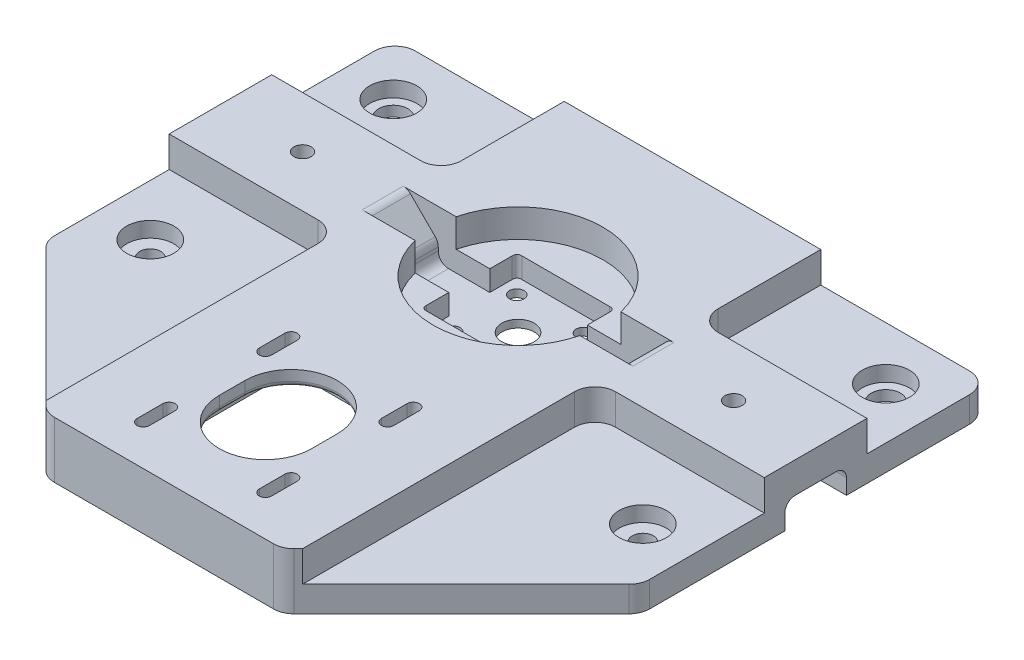
SolidWorks part; units mm, degrees
ref_plane "Front Plane" through (0, 0, 0) normal (0, 0, 1) x (1, 0, 0)
ref_plane "Top Plane" through (0, 0, 0) normal (0, 1, 0) x (1, 0, 0)
ref_plane "Right Plane" through (0, 0, 0) normal (1, 0, 0) x (0, 0, -1)
sketch "Sketch2" plane through (0, 0, 0) normal (0, 1, 0) x (1, 0, 0)
  line L2 (0, 33.02) -> (0, 0)
  line L3 (0, 0) -> (22.86, 0) construction
  line L4 (22.86, 0) -> (55.901, 38.5867) construction
  line L5 (55.901, 38.5867) -> (106.701, 38.5867) construction
  line L6 (106.701, 38.5867) -> (106.701, 56.3667)
  line L7 (0, 86.36) -> (0, 53.34)
  line L9 (0, 86.36) -> (20.32, 86.36)
  line L10 (20.32, 86.36) -> (106.701, 56.3667) construction
  line L11 (0, 53.34) -> (0, 33.02)
  line L12 (22.86, 0) -> (147.32, 0) construction
  line L13 (147.32, 0) -> (147.32, 86.36)
  line L14 (147.32, 86.36) -> (20.32, 86.36)
  line L15 (134.62, 73.2536) -> (134.62, 13.1064) construction
  line L16 (12.7, 73.2536) -> (134.62, 73.2536) construction
  line L17 (12.7, 73.2536) -> (12.7, 13.1064) construction
  line L18 (12.7, 13.1064) -> (134.62, 13.1064) construction
  line L19 (0, 0) -> (44.45, -44.45)
  line L20 (44.45, -44.45) -> (102.87, -44.45)
  line L21 (102.87, -44.45) -> (147.32, 0)
  line L22 (12.7, 73.2536) -> (0, 73.2536) construction
  line L23 (134.62, 73.2536) -> (147.32, 73.2536) construction
  line L24 (12.7, 13.1064) -> (12.7, 0) construction
  line L25 (12.7, 73.2536) -> (12.7, 86.36) construction
  circle A2 centre (12.7, 13.1064) radius 2.6035
  circle A3 centre (12.7, 73.2536) radius 3.6195
  circle A4 centre (73.681, 48.7467) radius 2.54 construction
  circle A5 centre (134.62, 73.2536) radius 3.6195
  circle A6 centre (134.62, 13.1064) radius 2.6035
  dimension "D11" = 121.92
  dimension "D20" = 7.239
  dimension "D22" = 5.08
  dimension "D9" = 5.207
  dimension "D1" = 50.8
  dimension "D2" = 50.8
  dimension "D3" = 22.86
  dimension "D4" = 33.02
  dimension "D5" = 20.32
  dimension "D6" = 20.32
  dimension "D7" = 91.44
  dimension "D8" = 17.78
  dimension "D12" = 60.1472
  dimension "D13" = 45
  dimension "D14" = 44.45
  dimension "D21" = 10.16
  dimension "D23" = 33.02
  dimension "D24" = 147.32
extrude "Boss-Extrude1" add sketch "Sketch2" along normal blind 6.35 contours L13 L14 L9 L7 L11 L2 L3 L12 A6 A5 A3 A2 region at (73.66, 0, -26.545)
sketch "Sketch3" plane through (0, 6.35, 0) normal (0, 1, 0) x (1, 0, 0)
  line L0 (12.7, 73.2536) -> (12.7, 13.1064) construction
  line L1 (134.62, 43.18) -> (12.7, 43.18) construction
  line L2 (134.62, 13.1064) -> (134.62, 73.2536) construction
  line L3 (0, 86.36) -> (0, 0) construction
  line L4 (147.32, 0) -> (147.32, 86.36) construction
  circle A0 centre (20.32, 43.18) radius 2.1273
  circle A1 centre (127, 43.18) radius 2.1273
  dimension "D1" = 4.2545
  dimension "D2" = 4.2545
  dimension "D3" = 20.32
  dimension "D4" = 20.32
extrude "Cut-Extrude1" cut sketch "Sketch3" against normal through all
sketch "Sketch4" plane through (0, 6.35, 0) normal (0, 1, 0) x (1, 0, 0)
  line L0 (20.32, 43.18) -> (127, 43.18) construction
  circle A0 centre (73.66, 43.18) radius 4.0005
  dimension "D1" = 8.001
extrude "Cut-Extrude2" cut sketch "Sketch4" against normal through all
sketch "Sketch5" plane through (0, 6.35, 0) normal (0, 1, 0) x (1, 0, 0)
  line L0 (147.32, 86.36) -> (0, 86.36) construction
  line L2 (41.91, 0) -> (41.91, 86.36) construction
  line L3 (41.91, 86.36) -> (105.41, 86.36)
  line L4 (105.41, 0) -> (105.41, 86.36) construction
  line L5 (41.91, 0) -> (105.41, 86.36) construction
  line L6 (41.91, 86.36) -> (105.41, 0) construction
  line L13 (44.45, -44.45) -> (102.87, -44.45) construction
  line L14 (44.45, -44.45) -> (102.87, -44.45)
  line L16 (105.41, 0) -> (105.41, -41.91)
  line L17 (102.87, -44.45) -> (147.32, 0) construction
  line L18 (105.41, -41.91) -> (102.87, -44.45)
  line L19 (41.91, 0) -> (41.91, -41.91)
  line L20 (0, 0) -> (44.45, -44.45) construction
  line L21 (41.91, -41.91) -> (44.45, -44.45)
  line L22 (0, 55.88) -> (0, 30.48)
  line L23 (0, 86.36) -> (0, 0) construction
  line L24 (0, 30.48) -> (41.91, 30.48)
  line L25 (41.91, 30.48) -> (41.91, 0)
  line L26 (0, 55.88) -> (41.91, 55.88)
  line L27 (41.91, 55.88) -> (41.91, 86.36)
  line L28 (105.41, 86.36) -> (105.41, 55.88)
  line L29 (105.41, 55.88) -> (147.32, 55.88)
  line L30 (147.32, 0) -> (147.32, 86.36) construction
  line L31 (147.32, 55.88) -> (147.32, 30.48)
  line L32 (147.32, 30.48) -> (105.41, 30.48)
  line L33 (105.41, 30.48) -> (105.41, 0)
  line L34 (127, 43.18) -> (147.32, 43.18) construction
  line L35 (0, 43.18) -> (20.32, 43.18) construction
  line L36 (20.32, 43.18) -> (127, 43.18) construction
  circle A0 centre (73.66, 43.18) radius 4.0005
  circle A1 centre (73.66, 43.18) radius 4.0005 construction
  point P0 (73.66, 43.18)
  dimension "D1" = 63.5
  dimension "D2" = 25.4
extrude "Boss-Extrude2" add sketch "Sketch5" along normal blind 7.62
fillet "Fillet3" radius 5.08 10 edges at (0, 3.175, -86.36) (147.32, 3.175, -86.36) (102.87, 6.985, 44.45) (44.45, 6.985, 44.45) (147.32, 3.175, 0) (0, 3.175, 0) (105.41, 10.16, -55.88) (105.41, 10.16, -30.48) (41.91, 10.16, -55.88) (41.91, 10.16, -30.48)
sketch "Sketch6" plane through (0, 6.35, 0) normal (0, 1, 0) x (1, 0, 0)
  circle A0 centre (12.7, 73.2536) radius 5.842
  circle A1 centre (12.7, 13.1064) radius 5.842
  circle A2 centre (134.62, 73.2536) radius 5.842
  circle A3 centre (134.62, 13.1064) radius 5.842
  dimension "D2" = 11.684
extrude "Countersinks" cut sketch "Sketch6" against normal blind 3.81
sketch "Sketch8" plane through (0, 13.97, 0) normal (0, 1, 0) x (1, 0, 0)
  circle A0 centre (73.66, 43.18) radius 21.0185
  circle A1 centre (73.66, 43.18) radius 4.0005
  circle A2 centre (73.66, 43.18) radius 4.0005 construction
  dimension "D1" = 42.037
extrude "Bearing Space" cut sketch "Sketch8" against normal blind 6.985
sketch "Sketch9" plane through (0, 6.985, 0) normal (0, 1, 0) x (1, 0, 0)
  line L1 (61.595, 54.991) -> (85.725, 54.991)
  line L2 (61.595, 54.991) -> (61.595, 31.369)
  line L3 (61.595, 31.369) -> (85.725, 31.369)
  line L4 (85.725, 54.991) -> (85.725, 31.369)
  line L5 (61.595, 54.991) -> (85.725, 31.369) construction
  line L6 (61.595, 31.369) -> (85.725, 54.991) construction
  circle A0 centre (73.66, 43.18) radius 4.0005
  circle A2 centre (73.66, 43.18) radius 4.0005 construction
  dimension "D1" = 24.13
  dimension "D2" = 23.622
extrude "Rotary Encoder Space" cut sketch "Sketch9" against normal blind 5.08
fillet "Fillet4" radius 1.27 4 edges at (61.595, 4.445, -31.369) (61.595, 4.445, -54.991) (85.725, 4.445, -31.369) (85.725, 4.445, -54.991) curvature continuous yes
sketch "Sketch10" plane through (0, 1.905, 0) normal (0, 1, 0) x (1, 0, 0)
  line L1 (65.4177, 51.1048) -> (81.9023, 51.1048) construction
  line L2 (65.4177, 51.1048) -> (65.4177, 35.2552) construction
  line L3 (65.4177, 35.2552) -> (81.9023, 35.2552) construction
  line L4 (81.9023, 51.1048) -> (81.9023, 35.2552) construction
  line L5 (65.4177, 51.1048) -> (81.9023, 35.2552) construction
  line L6 (65.4177, 35.2552) -> (81.9023, 51.1048) construction
  line L7 (61.849, 54.6735) -> (85.471, 54.6735) construction
  line L8 (61.849, 54.6735) -> (61.849, 31.6865) construction
  line L9 (61.849, 31.6865) -> (85.471, 31.6865) construction
  line L10 (85.471, 54.6735) -> (85.471, 31.6865) construction
  line L11 (61.849, 54.6735) -> (85.471, 31.6865) construction
  line L12 (61.849, 31.6865) -> (85.471, 54.6735) construction
  circle A0 centre (81.9023, 51.1048) radius 1.7907
  circle A1 centre (81.9023, 35.2552) radius 1.7907
  circle A2 centre (65.4177, 35.2552) radius 1.7907
  circle A3 centre (65.4177, 51.1048) radius 1.7907
  point P0 (73.66, 43.18)
  point P10 (73.66, 43.18)
  point P15 (83.693, 51.1048)
  point P16 (81.9023, 52.8955)
  dimension "D1" = 3.5814
  dimension "D2" = 22.987
  dimension "D3" = 23.622
  dimension "D4" = 1.778
  dimension "D5" = 1.778
extrude "Cut-Extrude7" cut sketch "Sketch10" against normal through all
sketch "Sketch11" plane through (0, 0, 0) normal (0, -1, 0) x (1, 0, 0)
  line L0 (73.66, 16.1671) -> (73.66, -43.18) construction
  line L1 (52.07, -8.7249) -> (95.25, -8.7249)
  line L2 (52.07, -8.7249) -> (52.07, 41.0591)
  line L3 (52.07, 41.0591) -> (95.25, 41.0591)
  line L4 (95.25, -8.7249) -> (95.25, 41.0591)
  line L5 (52.07, -8.7249) -> (95.25, 41.0591) construction
  line L6 (52.07, 41.0591) -> (95.25, -8.7249) construction
  line L7 (73.66, 19.3421) -> (73.66, 12.9921) construction
  line L8 (85.09, 19.3421) -> (85.09, 12.9921)
  line L9 (62.23, 19.3421) -> (62.23, 12.9921)
  line L10 (73.66, 4.7371) -> (73.66, 1.5621) construction
  circle A0 centre (73.66, 16.1671) radius 11.43 construction
  arc A1 (85.09, 19.3421) -> (62.23, 19.3421) centre (73.66, 19.3421) ccw
  arc A2 (62.23, 12.9921) -> (85.09, 12.9921) centre (73.66, 12.9921) ccw
  point P0 (73.66, 16.1671)
  point P5 (73.66, -43.18)
  point P12 (73.66, 16.1671)
  dimension "D3" = 22.86
  dimension "D1" = 59.3471
  dimension "D2" = 43.18
  dimension "D4" = 6.35
  dimension "D5" = 3.175
  dimension "D6" = 49.784
extrude "Cut-Extrude8" cut sketch "Sketch11" against normal blind 10.16
extrude "Cut-Extrude9" cut sketch "Sketch11<2>" against normal through all contours A0 | A2 L8 A1 L9
sketch "Sketch11<2>" plane through (0, 0, 0) normal (0, -1, 0) x (1, 0, 0) same geometry as "Sketch11"
fillet "Fillet7" radius 1.27 10 edges at (52.07, 10.16, 16.1671) (95.25, 10.16, 16.1671) (95.25, 5.08, -8.7249) (95.25, 5.08, 41.0591) (52.07, 5.08, 41.0591) (52.07, 5.08, -8.7249) (62.23, 10.16, 16.1671) (73.66, 10.16, 1.5621) (85.09, 10.16, 16.1671) (73.66, 10.16, 30.7721)
sketch "Sketch13" plane through (0, 13.97, 0) normal (0, 1, 0) x (1, 0, 0)
  line L0 (88.773, -4.2291) -> (88.773, 2.1209) construction
  line L1 (52.705, 4.7879) -> (94.615, 4.7879) construction
  line L2 (52.705, 4.7879) -> (52.705, -37.1221) construction
  line L3 (52.705, -37.1221) -> (94.615, -37.1221) construction
  line L4 (94.615, 4.7879) -> (94.615, -37.1221) construction
  line L5 (52.705, 4.7879) -> (94.615, -37.1221) construction
  line L6 (52.705, -37.1221) -> (94.615, 4.7879) construction
  line L7 (58.547, -31.2801) -> (88.773, -31.2801) construction
  line L8 (58.547, -31.2801) -> (58.547, -1.0541) construction
  line L9 (58.547, -1.0541) -> (88.773, -1.0541) construction
  line L10 (88.773, -31.2801) -> (88.773, -1.0541) construction
  line L11 (58.547, -31.2801) -> (88.773, -1.0541) construction
  line L12 (58.547, -1.0541) -> (88.773, -31.2801) construction
  line L13 (87.249, -4.2291) -> (87.249, 2.1209)
  line L14 (90.297, -4.2291) -> (90.297, 2.1209)
  line L15 (58.547, -4.2291) -> (58.547, 2.1209) construction
  line L16 (57.023, -4.2291) -> (57.023, 2.1209)
  line L17 (60.071, -4.2291) -> (60.071, 2.1209)
  line L18 (58.547, -34.4551) -> (58.547, -28.1051) construction
  line L19 (57.023, -34.4551) -> (57.023, -28.1051)
  line L20 (60.071, -34.4551) -> (60.071, -28.1051)
  line L21 (88.773, -34.4551) -> (88.773, -28.1051) construction
  line L22 (87.249, -34.4551) -> (87.249, -28.1051)
  line L23 (90.297, -34.4551) -> (90.297, -28.1051)
  line L24 (62.23, -16.1671) -> (85.09, -16.1671) construction
  line L25 (62.23, -19.3421) -> (62.23, -12.9921) construction
  line L26 (85.09, -19.3421) -> (85.09, -12.9921) construction
  circle A0 centre (88.773, -1.0541) radius 1.524 construction
  circle A1 centre (88.773, -31.2801) radius 1.524 construction
  circle A2 centre (58.547, -31.2801) radius 1.524 construction
  circle A3 centre (58.547, -1.0541) radius 1.524 construction
  arc A4 (87.249, -4.2291) -> (90.297, -4.2291) centre (88.773, -4.2291) ccw
  arc A5 (90.297, 2.1209) -> (87.249, 2.1209) centre (88.773, 2.1209) ccw
  arc A6 (57.023, -4.2291) -> (60.071, -4.2291) centre (58.547, -4.2291) ccw
  arc A7 (60.071, 2.1209) -> (57.023, 2.1209) centre (58.547, 2.1209) ccw
  arc A8 (57.023, -34.4551) -> (60.071, -34.4551) centre (58.547, -34.4551) ccw
  arc A9 (60.071, -28.1051) -> (57.023, -28.1051) centre (58.547, -28.1051) ccw
  arc A10 (87.249, -34.4551) -> (90.297, -34.4551) centre (88.773, -34.4551) ccw
  arc A11 (90.297, -28.1051) -> (87.249, -28.1051) centre (88.773, -28.1051) ccw
  point P0 (73.66, -16.1671)
  point P6 (73.66, -16.1671)
  point P15 (88.773, 0.4699)
  point P16 (90.297, -1.0541)
  point P19 (88.773, -1.0541)
  point P26 (58.547, -1.0541)
  point P32 (58.547, -31.2801)
  point P39 (88.773, -31.2801)
  dimension "D2" = 3.048
  dimension "D1" = 41.91
  dimension "D3" = 4.318
  dimension "D5" = 6.35
extrude "Cut-Extrude10" cut sketch "Sketch13" against normal through all
extrude "Cut-Extrude11" cut sketch "Sketch3<2>" along normal through all
sketch "Sketch3<2>" plane through (0, 6.35, 0) normal (0, 1, 0) x (1, 0, 0) same geometry as "Sketch3"
sketch "Sketch14" plane through (0, 0, 0) normal (0, -1, 0) x (1, 0, 0)
  line L0 (0, -50.8) -> (0, -35.56)
  line L1 (0, -81.28) -> (0, -2.1042) construction
  line L2 (0, -35.56) -> (43.18, -35.56)
  line L3 (43.18, -35.56) -> (43.18, -50.8)
  line L4 (43.18, -50.8) -> (0, -50.8)
  line L6 (20.32, -43.18) -> (0, -43.18) construction
  line L7 (20.32, -43.18) -> (127, -43.18) construction
  line L8 (127, -43.18) -> (147.32, -43.18) construction
  line L10 (147.32, -2.1042) -> (147.32, -81.28) construction
  line L11 (147.32, -50.8) -> (147.32, -35.56)
  line L12 (147.32, -35.56) -> (104.14, -35.56)
  line L13 (104.14, -35.56) -> (104.14, -50.8)
  line L14 (104.14, -50.8) -> (147.32, -50.8)
  point P4 (0, -43.18)
  dimension "D1" = 43.18
  dimension "D2" = 15.24
extrude "Cut-Extrude12" cut sketch "Sketch14" against normal blind 6.35
fillet "Fillet8" radius 2.54 10 edges at (104.14, 3.175, -35.56) (104.14, 3.175, -50.8) (43.18, 3.175, -35.56) (43.18, 3.175, -50.8) (104.14, 6.35, -43.18) (125.73, 6.35, -35.56) (125.73, 6.35, -50.8) (21.59, 6.35, -35.56) (43.18, 6.35, -43.18) (21.59, 6.35, -50.8)
sketch "Sketch15" plane through (0, 1.905, 0) normal (0, 1, 0) x (1, 0, 0)
  line L0 (52.6415, 43.18) -> (52.6415, 48.26) construction
  line L1 (98.4885, 38.1) -> (48.8315, 38.1)
  line L2 (98.4885, 38.1) -> (98.4885, 48.26)
  line L3 (98.4885, 48.26) -> (48.8315, 48.26)
  line L4 (48.8315, 38.1) -> (48.8315, 48.26)
  line L5 (98.4885, 38.1) -> (48.8315, 48.26) construction
  line L6 (98.4885, 48.26) -> (48.8315, 38.1) construction
  line L7 (52.6415, 43.18) -> (73.66, 43.18) construction
  circle A0 centre (73.66, 43.18) radius 21.0185 construction
  point P0 (73.66, 43.18)
  point P6 (73.66, 43.18)
  point P7 (52.6415, 43.18)
  dimension "D1" = 10.16
  dimension "D2" = 3.81
extrude "Cut-Extrude13" cut sketch "Sketch15" along normal through all
chamfer "Chamfer1" distance 7.62 angle 45 2 edges at (98.4885, 13.97, -43.18) (48.8315, 13.97, -43.18)
fillet "Fillet9" radius 2.54 6 edges at (106.1085, 13.97, -43.18) (98.4885, 6.35, -43.18) (98.4885, 1.905, -43.18) (48.8315, 6.35, -43.18) (48.8315, 1.905, -43.18) (41.2115, 13.97, -43.18)
